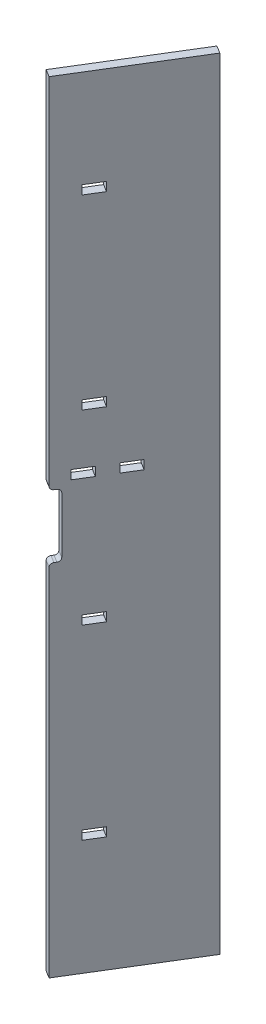
SolidWorks part; units mm, degrees
ref_plane "Front Plane" through (0, 0, 0) normal (0, 0, 1) x (1, 0, 0)
ref_plane "Top Plane" through (0, 0, 0) normal (0, 1, 0) x (1, 0, 0)
ref_plane "Right Plane" through (0, 0, 0) normal (1, 0, 0) x (0, 0, -1)
sketch "Sketch2" plane through (-119.8987, 0, -90.0076) normal (0, 1, 0) x (-0.8523, 0, -0.523)
  line L1 (-38.1, -44.45) -> (-44.45, -44.45)
  line L2 (-38.1, -44.45) -> (-38.1, 44.45)
  line L3 (-38.1, 44.45) -> (-44.45, 44.45)
  line L4 (-44.45, -44.45) -> (-44.45, 44.45)
  dimension "D1" = 6.35
  dimension "D2" = 88.9
extrude "Boss-Extrude1" add sketch "Sketch2" along normal blind 558.8
sketch "Sketch3" plane through (-89.338, 0, -54.8228) normal (0.8523, 0, 0.523) x (0.523, 0, -0.8523)
  line L1 (-19.05, 313.305) -> (-6.35, 313.305)
  line L2 (-19.05, 313.305) -> (-19.05, 306.955)
  line L3 (-19.05, 306.955) -> (-6.35, 306.955)
  line L4 (-6.35, 313.305) -> (-6.35, 306.955)
  line L5 (6.35, 313.305) -> (19.05, 313.305)
  line L6 (6.35, 313.305) -> (6.35, 306.955)
  line L7 (6.35, 306.955) -> (19.05, 306.955)
  line L8 (19.05, 313.305) -> (19.05, 306.955)
  line L10 (0, 310.13) -> (38.2669, 310.13) construction
  line L11 (-25.2474, 306.955) -> (48.5256, 306.955) construction
  dimension "D1" = 12.7
  dimension "D2" = 6.35
  dimension "D3" = 6.35
  dimension "D4" = 12.7
  dimension "D5" = 12.7
extrude "Cut-Extrude1" cut sketch "Sketch3" against normal through all
sketch "Sketch4" plane through (-89.338, 0, -54.8228) normal (0.8523, 0, 0.523) x (0.523, 0, -0.8523)
  line L0 (-30.4456, 558.8) -> (-30.4456, 0) construction
  line L1 (-30.4456, 302.2941) -> (-23.8294, 302.2941)
  line L2 (-30.4456, 302.2941) -> (-30.4456, 257.1391)
  line L3 (-30.4456, 257.1391) -> (-23.8294, 257.1391)
  line L4 (-23.8294, 302.2941) -> (-23.8294, 257.1391)
extrude "Cut-Extrude2" cut sketch "Sketch4" against normal through all and the other way through all
fillet "Fillet1" radius 2.54 4 edges at (-107.968, 257.1391, -30.5342) (-104.5076, 257.1391, -36.1733) (-107.968, 302.2941, -30.5342) (-104.5076, 302.2941, -36.1733)
sketch "Sketch5" plane through (-94.7502, 0, -58.1441) normal (-0.8523, 0, -0.523) x (-0.523, 0, 0.8523)
  line L1 (13.2344, 488.95) -> (0.5362, 488.95)
  line L2 (13.2344, 488.95) -> (13.2344, 482.6)
  line L3 (13.2344, 482.6) -> (0.5362, 482.6)
  line L4 (0.5362, 488.95) -> (0.5362, 482.6)
extrude "Cut-Extrude3" cut sketch "Sketch5" against normal through all
pattern_linear "LPattern1" count 4 spacing 133.35 along (0, -1, 0) of "Cut-Extrude3"
